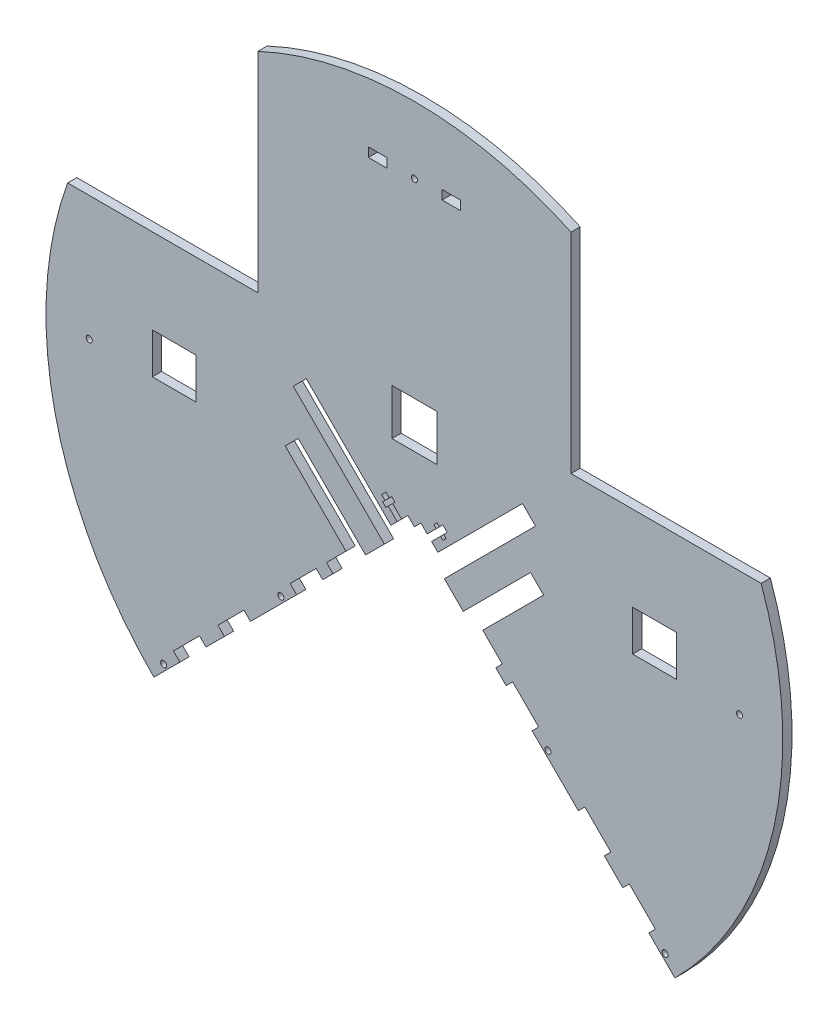
SolidWorks part; units mm, degrees
ref_plane "Front Plane" through (0, 0, 0) normal (0, 0, 1) x (1, 0, 0)
ref_plane "Top Plane" through (0, 0, 0) normal (0, 1, 0) x (1, 0, 0)
ref_plane "Right Plane" through (0, 0, 0) normal (1, 0, 0) x (0, 0, -1)
sketch "Sketch1" plane through (0, 0, 0) normal (0, 0, 1) x (1, 0, 0)
  circle A0 centre (0, -210.9923) radius 254
extrude "Boss-Extrude1" add sketch "Sketch1" along normal blind 6.35 contours A0
sketch "Sketch3" plane through (0, 0, 0) normal (0, 0, -1) x (-1, 0, 0)
  line L0 (179.6051, -390.5974) -> (0, -210.9923)
  line L1 (0, -210.9923) -> (-179.6051, -390.5974)
  line L2 (91.3112, -302.3035) -> (113.0075, -323.9998) construction
  line L3 (-179.6051, -390.5974) -> (-172.1335, -383.1258) construction
  circle A0 centre (0, -210.9923) radius 254 construction
  arc A1 (179.6051, -390.5974) -> (-179.6051, -390.5974) centre (0, -210.9923) cw
extrude "Cut-Extrude1" cut sketch "Sketch3" against normal through all
sketch "Sketch4" plane through (0, 0, 6.35) normal (0, 0, 1) x (1, 0, 0)
  line L0 (-161.6446, -372.6369) -> (-166.1347, -368.1468)
  line L1 (-161.6446, -372.6369) -> (-143.6841, -354.6764)
  line L2 (-166.1347, -368.1468) -> (-148.1742, -350.1862)
  line L3 (-143.6841, -354.6764) -> (-148.1742, -350.1862)
  line L4 (-179.6051, -390.5974) -> (0, -210.9923) construction
  line L5 (-166.1347, -368.1468) -> (-161.6446, -372.6369) construction
  line L7 (-130.9681, -341.9603) -> (-135.4582, -337.4702)
  line L8 (-130.9681, -341.9603) -> (-113.0075, -323.9998)
  line L9 (-135.4582, -337.4702) -> (-117.4977, -319.5097)
  line L10 (-113.0075, -323.9998) -> (-117.4977, -319.5097)
  line L11 (-81.1905, -292.1828) -> (-85.6806, -287.6926)
  line L12 (-81.1905, -292.1828) -> (-63.23, -274.2223)
  line L13 (-85.6806, -287.6926) -> (-67.7201, -269.7321)
  line L14 (-63.23, -274.2223) -> (-67.7201, -269.7321)
  line L15 (-85.6806, -287.6926) -> (-81.1905, -292.1828) construction
  line L17 (-56.1266, -267.1189) -> (-60.6167, -262.6287)
  line L18 (-56.1266, -267.1189) -> (-33.676, -244.6682)
  line L19 (-60.6167, -262.6287) -> (-38.1661, -240.1781)
  line L20 (-33.676, -244.6682) -> (-38.1661, -240.1781)
  line L21 (-11.6893, -222.6816) -> (-16.1795, -218.1915)
  line L22 (-11.6893, -222.6816) -> (0, -210.9923)
  line L23 (-16.1795, -218.1915) -> (-4.4901, -206.5021)
  line L24 (0, -210.9923) -> (-4.4901, -206.5021)
  line L25 (-16.1795, -218.1915) -> (-11.6893, -222.6816) construction
  line L27 (-143.6841, -354.6764) -> (-148.1742, -350.1862) construction
  line L28 (-135.4582, -337.4702) -> (-130.9681, -341.9603) construction
  line L29 (-113.0075, -323.9998) -> (-117.4977, -319.5097) construction
  line L30 (-63.23, -274.2223) -> (-67.7201, -269.7321) construction
  line L31 (0, -210.9923) -> (-4.4901, -206.5021) construction
  line L32 (-60.6167, -262.6287) -> (-38.1661, -240.1781) construction
  line L33 (-60.6167, -262.6287) -> (-56.1266, -267.1189) construction
  line L34 (-38.1661, -240.1781) -> (-33.676, -244.6682) construction
extrude "Cut-Extrude2" cut sketch "Sketch4" against normal through all
mirror "Mirror1" about plane through (0, 0, 0) normal (1, 0, 0) of "Cut-Extrude2"
sketch "Sketch6" plane through (0, 0, 6.35) normal (0, 0, 1) x (1, 0, 0)
  line L0 (-189.391, -362.851) -> (-147.7076, -404.5344) construction
  line L1 (-176.6237, -378.6357) -> (-172.1335, -383.1258) construction
  line L2 (-173.6063, -375.6183) -> (-169.1162, -380.1085) construction
  line L3 (-136.5306, -343.0327) -> (-168.0044, -374.5065) construction
  line L4 (-148.1742, -350.1862) -> (-166.1347, -368.1468) construction
  line L5 (-143.6841, -354.6764) -> (-130.9681, -341.9603) construction
  line L6 (-119.5963, -271.0011) -> (-74.6896, -315.9078) construction
  line L7 (-95.8014, -297.8134) -> (-91.3112, -302.3035) construction
  line L8 (-92.784, -294.796) -> (-88.2939, -299.2862) construction
  circle A0 centre (-172.8699, -379.3721) radius 2.0955
  circle A1 centre (-92.0476, -298.5498) radius 2.0955
  dimension "D1" = 4.191
extrude "Cut-Extrude4" cut sketch "Sketch6" against normal through all
mirror "Mirror2" about plane through (0, 0, 0) normal (1, 0, 0) of "Cut-Extrude4"
sketch "Sketch8" plane through (0, 0, 6.35) normal (0, 0, 1) x (1, 0, 0)
  line L0 (-20.6696, -231.6619) -> (-11.6893, -222.6816)
  line L1 (-20.6696, -231.6619) -> (-83.5314, -168.8001)
  line L2 (-11.6893, -222.6816) -> (-74.5511, -159.8198)
  line L3 (-83.5314, -168.8001) -> (-74.5511, -159.8198)
  line L4 (-33.676, -244.6682) -> (-11.6893, -222.6816) construction
  line L5 (-8.7612, -234.5899) -> (-94.7474, -148.6038) construction
  line L6 (-77.7195, -170.1218) -> (-52.225, -195.6163) construction
  line L7 (-73.2293, -165.6317) -> (-47.7349, -191.1262) construction
  line L8 (-16.1795, -218.1915) -> (-11.6893, -222.6816) construction
  dimension "D1" = 88.9
extrude "Cut-Extrude6" cut sketch "Sketch8" against normal through all
mirror "Mirror3" about plane through (0, 0, 0) normal (1, 0, 0) of "Cut-Extrude6"
sketch "Sketch9" plane through (0, 0, 6.35) normal (0, 0, 1) x (1, 0, 0)
  line L0 (-28.1989, -194.4827) -> (-15.046, -207.6356) construction
  line L1 (-4.4901, -206.5021) -> (0, -210.9923) construction
  line L2 (-16.1795, -218.1915) -> (-11.6893, -222.6816) construction
  line L3 (-4.4901, -206.5021) -> (-16.1795, -218.1915) construction
  line B0 (-11.8435, -213.8555) -> (-8.8261, -210.8381)
  line B1 (-17.2675, -202.3967) -> (-15.6331, -200.7623)
  line B2 (-15.6331, -200.7623) -> (-13.3881, -203.0073)
  line B3 (-13.3881, -203.0073) -> (-15.0225, -204.6417)
  line B4 (-15.0225, -204.6417) -> (-8.8261, -210.8381)
  line B5 (-17.2675, -202.3967) -> (-19.6024, -200.0618)
  line B6 (-19.6024, -200.0618) -> (-22.6198, -203.0792)
  line B7 (-20.2849, -205.4141) -> (-22.6198, -203.0792)
  line B8 (-18.0398, -207.6591) -> (-11.8435, -213.8555)
  line B9 (-19.6743, -209.2935) -> (-18.0398, -207.6591)
  line B10 (-21.9193, -207.0485) -> (-19.6743, -209.2935)
  line B11 (-20.2849, -205.4141) -> (-21.9193, -207.0485)
sketch_block_instance "TSlot-1"
sketch_block "TSlot" parameters "D1"=3.302, "D2"=3.175
extrude "Cut-Extrude7" cut sketch "Sketch9" against normal through all
mirror "Mirror4" about plane through (0, 0, 0) normal (1, 0, 0) of "Cut-Extrude7"
sketch "Sketch10" plane through (0, 0, 6.35) normal (0, 0, 1) x (1, 0, 0)
  line L0 (-92.7156, -190.1188) -> (-17.7162, -265.1181) construction
  line L1 (-80.0807, -207.2437) -> (-42.6562, -244.6682) construction
  line L2 (-38.1661, -240.1781) -> (-75.5906, -202.7536) construction
  line L3 (-80.0807, -198.2635) -> (-89.061, -207.2437)
  line L4 (-80.0807, -198.2635) -> (-33.676, -244.6682)
  line L5 (-89.061, -207.2437) -> (-42.6562, -253.6485)
  line L6 (-33.676, -244.6682) -> (-42.6562, -253.6485)
  line L7 (-33.676, -244.6682) -> (-20.6696, -231.6619) construction
  line L8 (-75.5906, -202.7536) -> (-80.0807, -207.2437) construction
  dimension "D1" = 6.35
  dimension "D2" = 6.35
extrude "Cut-Extrude8" cut sketch "Sketch10" against normal through all
mirror "Mirror5" about plane through (0, 0, 0) normal (1, 0, 0) of "Cut-Extrude8"
sketch "Sketch12" plane through (0, 0, 0) normal (0, 0, -1) x (-1, 0, 0)
  line L0 (0, 43.0077) -> (0, -163.8394) construction
  line L1 (107.9506, -125.2137) -> (246.3055, -125.2137)
  line L2 (107.9506, -125.2137) -> (107.9506, 34.5324)
  line L3 (107.9506, 34.5324) -> (246.3055, 34.5324)
  line L4 (246.3055, -125.2137) -> (246.3055, 34.5324)
  line L5 (-246.3055, -125.2137) -> (-246.3055, 34.5324)
  line L6 (-107.9506, 34.5324) -> (-246.3055, 34.5324)
  line L7 (-107.9506, -125.2137) -> (-107.9506, 34.5324)
  line L8 (-107.9506, -125.2137) -> (-246.3055, -125.2137)
  arc A0 (179.6051, -390.5974) -> (-179.6051, -390.5974) centre (0, -210.9923) ccw construction
extrude "Cut-Extrude10" cut sketch "Sketch12" against normal through all
sketch "Sketch13" plane through (0, 0, 6.35) normal (0, 0, 1) x (1, 0, 0)
  line L0 (0, 43.0077) -> (0, -205.8735) construction
  line L1 (-180.6732, -183.7503) -> (-150.4381, -183.7503)
  line L2 (-180.6732, -183.7503) -> (-180.6732, -211.7731)
  line L3 (-180.6732, -211.7731) -> (-150.4381, -211.7731)
  line L4 (-150.4381, -183.7503) -> (-150.4381, -211.7731)
  line L5 (15.4863, -134.3417) -> (15.4863, -166.0517)
  line L6 (15.4863, -134.3417) -> (-15.4863, -134.3417)
  line L7 (0, -134.3417) -> (0, -166.0517)
  line L8 (15.4863, -166.0517) -> (-15.4863, -166.0517)
  line L9 (-15.4863, -134.3417) -> (-15.4863, -166.0517)
  line L11 (150.4381, -183.7503) -> (150.4381, -211.7731)
  line L12 (180.6732, -211.7731) -> (150.4381, -211.7731)
  line L13 (180.6732, -183.7503) -> (180.6732, -211.7731)
  line L14 (180.6732, -183.7503) -> (150.4381, -183.7503)
  arc A0 (107.9506, 18.9265) -> (-107.9506, 18.9265) centre (0, -210.9923) ccw construction
extrude "Cut-Extrude11" cut sketch "Sketch13" against normal through all contours L8 L5 L6 L7 | L6 L9 L8 L7 | L13 L14 L11 L12 | L4 L1 L2 L3 region at (-165.5556, -197.7617, 6.35) region at (7.7431, -150.1967, 6.35) region at (-7.7431, -150.1967, 6.35) region at (165.5556, -197.7617, 6.35)
sketch "Sketch17" plane through (0, 0, 6.35) normal (0, 0, 1) x (1, 0, 0)
  line L0 (220.98, -213.1132) -> (227.33, -213.1132) construction
  line L1 (220.98, -208.8714) -> (227.33, -208.8714) construction
  line L2 (31.75, -6.35) -> (31.75, 0) construction
  line L3 (19.05, -6.35) -> (31.75, -6.35) construction
  line L4 (19.05, -6.35) -> (19.05, 0) construction
  line L5 (19.05, 0) -> (31.75, 0) construction
  line L6 (2.1336, -6.35) -> (2.1336, 0) construction
  line L7 (-2.1336, -6.35) -> (-2.1336, 0) construction
  line L8 (-227.33, -213.1132) -> (-220.98, -213.1132) construction
  line L9 (-227.33, -208.8714) -> (-220.98, -208.8714) construction
  line L10 (220.98, -213.1132) -> (227.33, -213.1132) construction
  line L11 (220.98, -208.8714) -> (227.33, -208.8714) construction
  line L12 (31.75, -6.35) -> (31.75, 0)
  line L13 (19.05, -6.35) -> (31.75, -6.35)
  line L14 (19.05, -6.35) -> (19.05, 0)
  line L15 (19.05, 0) -> (31.75, 0)
  line L16 (2.1336, -6.35) -> (2.1336, 0) construction
  line L17 (-2.1336, -6.35) -> (-2.1336, 0) construction
  line L18 (-227.33, -213.1132) -> (-220.98, -213.1132) construction
  line L19 (-227.33, -208.8714) -> (-220.98, -208.8714) construction
  line L20 (224.155, -213.1132) -> (224.155, -208.8714) construction
  line L21 (220.98, -191.9423) -> (220.98, -179.2423) construction
  line L22 (227.33, -191.9423) -> (227.33, -179.2423) construction
  line L23 (-224.155, -213.1132) -> (-224.155, -208.8714) construction
  line L24 (-19.05, 0) -> (-31.75, 0)
  line L25 (-31.75, 0) -> (-31.75, -6.35)
  line L26 (-31.75, -6.35) -> (-19.05, -6.35)
  line L27 (-19.05, -6.35) -> (-19.05, 0)
  line L28 (-19.05, 0) -> (-31.75, 0)
  line L29 (-31.75, 0) -> (-31.75, -6.35)
  line L30 (-31.75, -6.35) -> (-19.05, -6.35)
  line L31 (-19.05, -6.35) -> (-19.05, 0)
  line L32 (-227.33, -191.9423) -> (-227.33, -179.2423) construction
  line L33 (-220.98, -191.9423) -> (-220.98, -179.2423) construction
  line L34 (-2.1336, -3.175) -> (2.1336, -3.175) construction
  circle A0 centre (224.155, -210.9923) radius 2.1209
  circle A1 centre (-224.155, -210.9923) radius 2.1209
  circle A2 centre (0, -3.175) radius 2.1336
  dimension "D1" = 0
extrude "Cut-Extrude12" cut sketch "Sketch17" against normal through all
